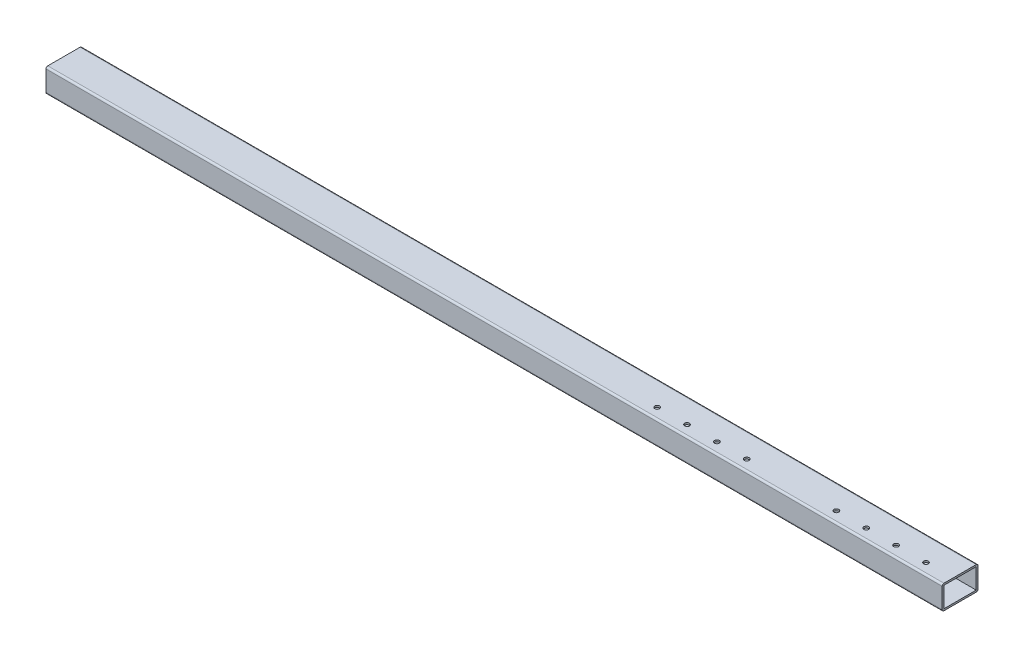
SolidWorks part; units mm, degrees
ref_plane "Спереди" through (0, 0, 0) normal (0, 0, 1) x (1, 0, 0)
ref_plane "Сверху" through (0, 0, 0) normal (0, 1, 0) x (1, 0, 0)
ref_plane "Справа" through (0, 0, 0) normal (1, 0, 0) x (0, 0, -1)
sketch "Эскиз1" plane through (0, 0, 0) normal (1, 0, 0) x (0, 0, -1)
  line L1 (-27, 20) -> (27, 20)
  line L2 (-30, 17) -> (-30, -17)
  line L3 (-27, -20) -> (27, -20)
  line L4 (30, 17) -> (30, -17)
  line L5 (-30, 20) -> (30, -20) construction
  line L6 (-30, -20) -> (30, 20) construction
  arc A0 (-27, 20) -> (-30, 17) centre (-27, 17) ccw
  arc A1 (-30, -17) -> (-27, -20) centre (-27, -17) ccw
  arc A2 (27, -20) -> (30, -17) centre (27, -17) ccw
  arc A3 (27, 20) -> (30, 17) centre (27, 17) cw
  point P0 (0, 0)
  dimension "D1" = 3
extrude "Вытянуть-Тонкостенный1" add sketch "Эскиз1" along normal blind 1500 thin thin type one direction reverse wall 3
sketch "Эскиз2" plane through (0, 20, 0) normal (0, 1, 0) x (1, 0, 0)
  circle A0 centre (1455, -12) radius 4.05
  circle A1 centre (1405, -12) radius 4.05
  circle A2 centre (1355, -12) radius 4.05
  circle A3 centre (1305, -12) radius 4.05
  circle A4 centre (1155, -12) radius 4.05
  circle A5 centre (1105, -12) radius 4.05
  circle A6 centre (1055, -12) radius 4.05
  circle A7 centre (1005, -12) radius 4.05
  dimension "D1" = 4
  dimension "D2" = 2
extrude "Вырез-Вытянуть1" cut sketch "Эскиз2" against normal through all
